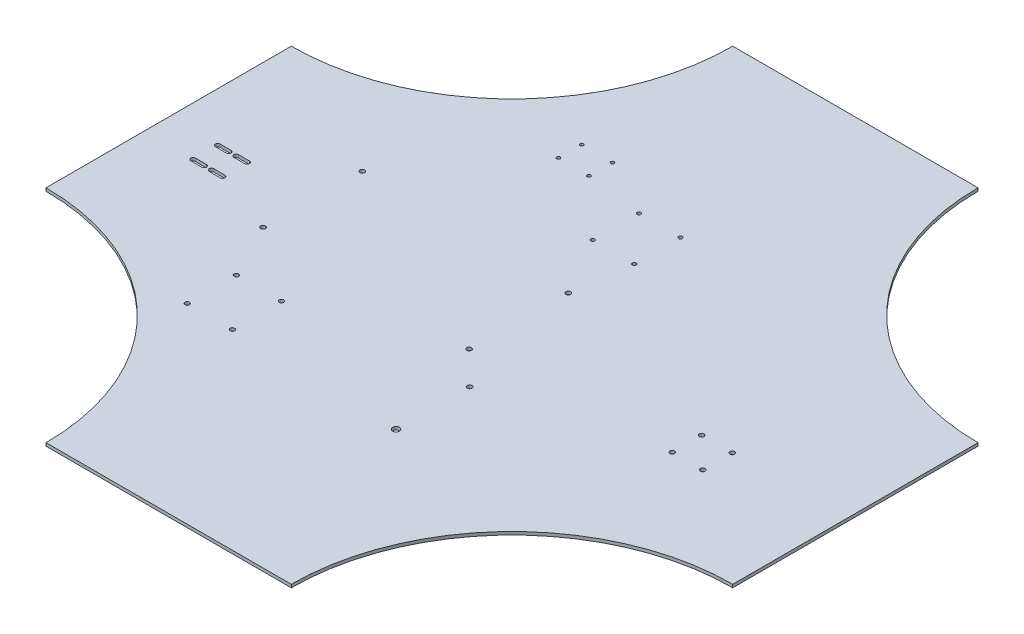
SolidWorks part; units mm, degrees
material "6061 Alloy"
ref_plane "Front Plane" through (0, 0, 0) normal (0, 0, 1) x (1, 0, 0)
ref_plane "Top Plane" through (0, 0, 0) normal (0, 1, 0) x (1, 0, 0)
ref_plane "Right Plane" through (0, 0, 0) normal (1, 0, 0) x (0, 0, -1)
sketch "Sketch1" plane through (0, 0, 0) normal (0, 1, 0) x (1, 0, 0)
  line L9 (-127, -355.6) -> (127, -355.6)
  line L10 (-355.6, -127) -> (-355.6, 127)
  line L11 (-127, 355.6) -> (127, 355.6)
  line L12 (355.6, -127) -> (355.6, 127)
  line L13 (-193.9554, -193.9554) -> (193.9554, 193.9554) construction
  line L14 (-193.9554, 193.9554) -> (193.9554, -193.9554) construction
  arc A8 (-355.6, 127) -> (-127, 355.6) centre (-355.6, 355.6) ccw
  arc A9 (127, 355.6) -> (355.6, 127) centre (355.6, 355.6) ccw
  arc A10 (355.6, -127) -> (127, -355.6) centre (355.6, -355.6) ccw
  arc A11 (-127, -355.6) -> (-355.6, -127) centre (-355.6, -355.6) ccw
  point P0 (0, 0)
  point P1 (0, 0)
  point P2 (0, 0)
  dimension "D3" = 457.2
  dimension "D4" = 457.2
  dimension "D5" = 457.2
  dimension "D6" = 457.2
  dimension "D1" = 711.2
  dimension "D2" = 711.2
extrude "Boss-Extrude1" add sketch "Sketch1" along normal blind 3.175
sketch "Sketch2" plane through (0, 3.175, 0) normal (0, 1, 0) x (1, 0, 0)
  line L0 (-304.8, 2.413) -> (-293.37, 2.413)
  line L1 (-304.8, -22.987) -> (-293.37, -22.987)
  line L2 (-293.37, -2.413) -> (-304.8, -2.413)
  line L3 (-285.75, -2.413) -> (-274.32, -2.413)
  line L4 (-285.75, -22.987) -> (-274.32, -22.987)
  line L5 (-274.32, 2.413) -> (-285.75, 2.413)
  line L6 (-293.37, -27.813) -> (-304.8, -27.813)
  line L7 (-355.6, 127) -> (-355.6, -127) construction
  line L8 (-274.32, -27.813) -> (-285.75, -27.813)
  arc A0 (-293.37, -2.413) -> (-293.37, 2.413) centre (-293.37, 0) ccw
  arc A1 (-274.32, -2.413) -> (-274.32, 2.413) centre (-274.32, 0) ccw
  arc A2 (-274.32, -27.813) -> (-274.32, -22.987) centre (-274.32, -25.4) ccw
  arc A3 (-293.37, -27.813) -> (-293.37, -22.987) centre (-293.37, -25.4) ccw
  arc A4 (-285.75, 2.413) -> (-285.75, -2.413) centre (-285.75, 0) ccw
  arc A5 (-304.8, 2.413) -> (-304.8, -2.413) centre (-304.8, 0) ccw
  arc A6 (-304.8, -22.987) -> (-304.8, -27.813) centre (-304.8, -25.4) ccw
  arc A7 (-285.75, -22.987) -> (-285.75, -27.813) centre (-285.75, -25.4) ccw
  dimension "D1" = 4.826
  dimension "D2" = 4.826
  dimension "D3" = 4.826
  dimension "D4" = 4.826
  dimension "D5" = 4.826
  dimension "D6" = 4.826
  dimension "D7" = 4.826
  dimension "D8" = 4.826
  dimension "D9" = 11.43
  dimension "D10" = 11.43
  dimension "D11" = 11.43
  dimension "D12" = 11.43
  dimension "D13" = 19.05
  dimension "D14" = 19.05
  dimension "D15" = 25.4
  dimension "D16" = 25.4
  dimension "D17" = 0
  dimension "D18" = 50.8
extrude "Cut-Extrude1" cut sketch "Sketch2" against normal through all both and the other way through all
sketch "Sketch4" plane through (0, 3.175, 0) normal (0, 1, 0) x (1, 0, 0)
  circle A0 centre (237.49, -9.4302) radius 2.413
  circle A1 centre (205.74, -9.4302) radius 2.413
  circle A2 centre (237.49, -39.9102) radius 2.413
  circle A3 centre (205.74, -39.9102) radius 2.413
extrude "Cut-Extrude2" cut sketch "Sketch4" against normal through all
sketch "Sketch5" plane through (0, 0, 0) normal (0, -1, 0) x (1, 0, 0)
  circle A0 centre (-207.7901, 50.0166) radius 2.5
  circle A1 centre (-206.624, -51.5767) radius 2.5
  circle A2 centre (8.0956, 52.4945) radius 2.478
  circle A3 centre (9.2617, -49.0988) radius 2.5
extrude "Cut-Extrude3" cut sketch "Sketch5" against normal through all
sketch "Sketch6" plane through (0, 0, 0) normal (0, -1, 0) x (1, 0, 0)
  circle A0 centre (-131.9657, 157.5947) radius 2.3218
  circle A1 centre (-131.9657, 106.7947) radius 2.3218
  circle A2 centre (-178.7006, 106.7947) radius 2.3218
  circle A3 centre (-178.7006, 157.5947) radius 2.3218
  circle A4 centre (42.2659, 162.3375) radius 3.5045
  circle A5 centre (42.2659, 86.1375) radius 2.5
  circle A6 centre (17.3717, -109.2657) radius 1.905
  circle A7 centre (-25.6811, -109.3842) radius 1.905
  circle A8 centre (-25.5498, -157.136) radius 1.905
  circle A9 centre (17.503, -157.0152) radius 1.905
  circle A10 centre (-84.8824, -188.8713) radius 1.75
  circle A11 centre (-85.0918, -164.8722) radius 1.75
  circle A12 centre (-116.8812, -189.1505) radius 1.75
  circle A13 centre (-117.0906, -165.1514) radius 1.75
extrude "Cut-Extrude4" cut sketch "Sketch6" against normal through all
